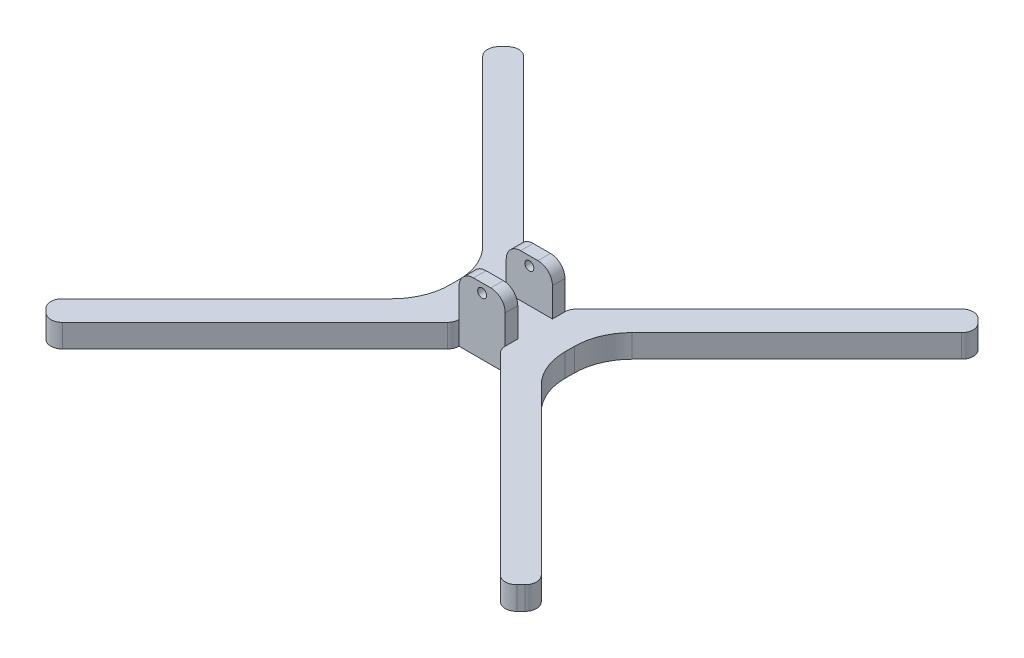
SolidWorks part; units mm, degrees
ref_plane "Front Plane" through (0, 0, 0) normal (0, 0, 1) x (1, 0, 0)
ref_plane "Top Plane" through (0, 0, 0) normal (0, 1, 0) x (1, 0, 0)
ref_plane "Right Plane" through (0, 0, 0) normal (1, 0, 0) x (0, 0, -1)
sketch "Sketch2" plane through (0, 0, 0) normal (0, 1, 0) x (1, 0, 0)
  line L1 (4, 6) -> (39.3553, 41.3553)
  line L2 (10, 4.9289) -> (42.8909, 37.8198)
  line L3 (39.3553, 41.3553) -> (42.8909, 37.8198)
  line L4 (0, -55) -> (0, 55) construction
  line L6 (-39.3553, 41.3553) -> (-42.8909, 37.8198)
  line L8 (-10, 4.9289) -> (-42.8909, 37.8198)
  line L9 (-4, 6) -> (-39.3553, 41.3553)
  line L10 (-55, 0) -> (55, 0) construction
  line L11 (39.3553, -41.3553) -> (42.8909, -37.8198)
  line L12 (10, -4.9289) -> (42.8909, -37.8198)
  line L13 (4, -6) -> (39.3553, -41.3553)
  line L16 (-10, -4.9289) -> (-42.8909, -37.8198)
  line L17 (-39.3553, -41.3553) -> (-42.8909, -37.8198)
  line L18 (-4, -6) -> (-39.3553, -41.3553)
  line L21 (-10, 4.9289) -> (-10, -4.9289)
  line L22 (10, 4.9289) -> (10, -4.9289)
  line L23 (-4, 6) -> (-4, 3)
  line L24 (-4, 3) -> (4, 3)
  line L25 (4, 6) -> (4, 3)
  line L26 (-4, -6) -> (-4, -3)
  line L27 (-4, -3) -> (4, -3)
  line L28 (4, -3) -> (4, -6)
  point P0 (0, 3)
  point P8 (-10, 0)
  point P18 (10, 0)
  point P25 (0, -3)
  dimension "D1" = 50
  dimension "D2" = 5
  dimension "D3" = 8
  dimension "D4" = 3
  dimension "D5" = 6
  dimension "D6" = 90
  dimension "D7" = 45
  dimension "D8" = 3
  dimension "D9" = 6
  dimension "D10" = 6
  dimension "D11" = 90
extrude "Boss-Extrude2" add sketch "Sketch2" along normal blind 4
fillet "Fillet1" radius 2 12 edges at (4, 2, -6) (4, 2, 6) (-4, 2, 6) (-4, 2, -6) (42.8909, 2, -37.8198) (39.3553, 2, -41.3553) (42.8909, 2, 37.8198) (39.3553, 2, 41.3553) (-39.3553, 2, 41.3553) (-42.8909, 2, 37.8198) (-39.3553, 2, -41.3553) (-42.8909, 2, -37.8198)
fillet "Fillet2" radius 10 4 edges at (-10, 2, 4.9289) (-10, 2, -4.9289) (10, 2, -4.9289) (10, 2, 4.9289)
scale "Echelle1" scale about centroid uniform scaling yes scale factor 2
sketch "Esquisse1" plane through (0, -2, 0) normal (0, -1, 0) x (1, 0, 0)
  line L0 (55, 0) -> (-55, 0) construction
  line L1 (-8, -6) -> (8, -6)
  line L2 (-8, -6) -> (-8, -10.3431)
  line L3 (-8, -10.3431) -> (8, -10.3431)
  line L4 (8, -6) -> (8, -10.3431)
  line L5 (8, 6) -> (8, 10.3431)
  line L6 (-8, 6) -> (8, 6)
  line L7 (-8, 6) -> (-8, 10.3431)
  line L8 (-8, 10.3431) -> (8, 10.3431)
extrude "Boss.-Extru.1" add sketch "Esquisse1" against normal offset from surface (23 mm away) 15 up to face at (0, 6, 0) offset beyond the face yes
sketch "Esquisse2" plane through (0, 0, -10.3431) normal (0, 0, -1) x (-1, 0, 0)
  line L0 (0, -3.175) -> (0, 49996.825) construction
  line L1 (8, -2) -> (-8, -2) construction
  circle A0 centre (0, 17.9559) radius 1.55
  point P6 (0, -2)
  dimension "D1" = 3.1
extrude "Enlèv. mat.-Extru.1" cut sketch "Esquisse2" against normal up to surface (20.6863 mm away) up to face at (0, 8.3333, 10.3431)
fillet "Congé1" radius 5 4 edges at (8, 21, -8.1716) (-8, 21, -8.1716) (-8, 21, 8.1716) (8, 21, 8.1716)
equation "\"ScrewSize\"= 3.1mm"
